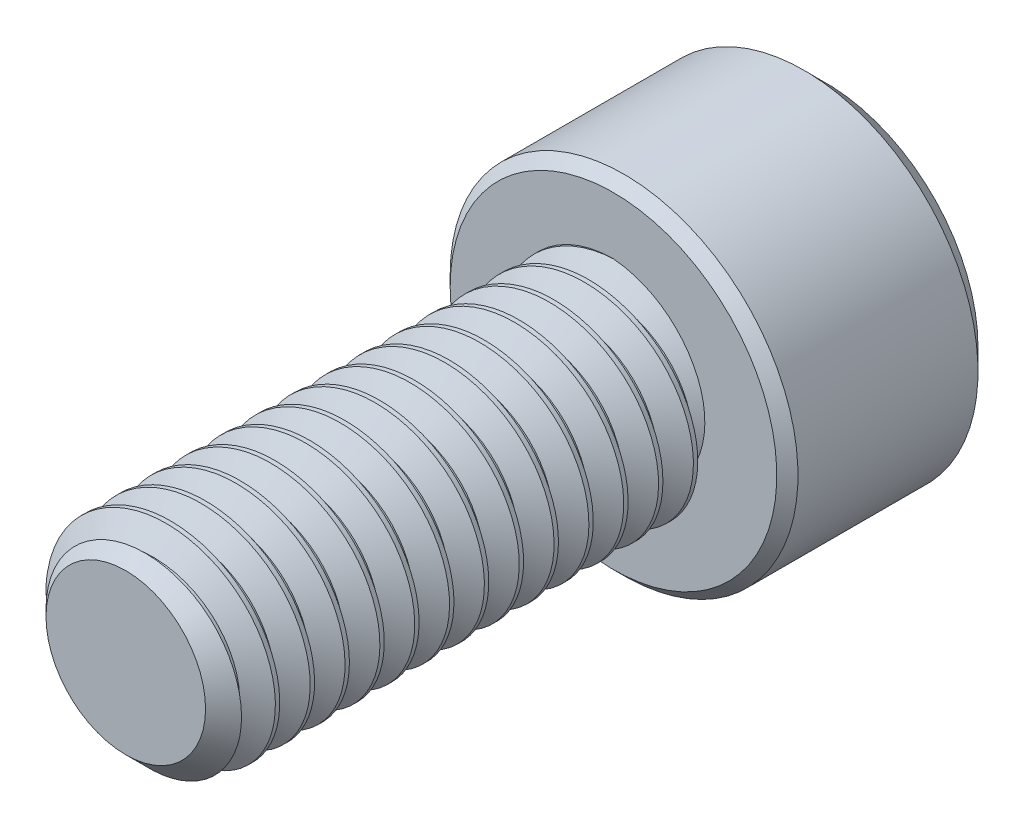
SolidWorks part; units mm, degrees
ref_plane "Front Plane" through (0, 0, 0) normal (0, 0, 1) x (1, 0, 0)
ref_plane "Top Plane" through (0, 0, 0) normal (0, 1, 0) x (1, 0, 0)
ref_plane "Right Plane" through (0, 0, 0) normal (1, 0, 0) x (0, 0, -1)
sketch "Sketch1" plane through (0, 0, 0) normal (0, 0, 1) x (1, 0, 0)
  line L0 (0, 2.413) -> (0, -2.413) construction
  circle A0 centre (0, 0) radius 2.413
  dimension "OD" = 4.826
extrude "Extrude1" add sketch "Sketch1" against normal blind 11.1125
sketch "Sketch2" plane through (0, 0, 0) normal (0, 0, 1) x (1, 0, 0)
  circle A0 centre (0, 0) radius 2.413 construction
  circle A1 centre (0, 0) radius 2.413
curve "Helix/Spiral1" pitch 0.7937 height 11.9062 turns 15 parameters "pitch"=0.7937
chamfer "Chamfer3" distance 0.5953 angle 45 1 edges at (2.413, 0, 0)
sketch "Sketch3" plane through (0, 0, 0) normal (1, 0, 0) x (0, 0, -1)
  line L0 (-0.6945, 2.413) -> (-0.3969, 1.8974)
  line L1 (-0.3969, 1.8974) -> (-0.2977, 1.8974)
  line L2 (-0.2977, 1.8974) -> (0, 2.413)
  line L3 (-0.6945, 2.413) -> (0, 2.413)
  line L4 (-0.3473, 2.413) -> (-0.3473, 1.8974) construction
  line L5 (-0.5457, 2.1552) -> (-0.1488, 2.1552) construction
  line L6 (0, 2.413) -> (0, -2.413) construction
  dimension "D1" = 0.0992
  dimension "D2" = 0.3969
  dimension "D3" = 60
sweep "Cut-Sweep1" cut profiles "Sketch3" path "Helix/Spiral1"
sketch "Sketch6" plane through (0, 0, -11.1125) normal (0, 0, -1) x (-1, 0, 0)
  circle A0 centre (0, 0) radius 3.9624
  dimension "head dia" = 7.9248
extrude "Extrude2" add sketch "Sketch6" along normal blind 4.826
sketch "Sketch7" plane through (0, 0, -15.9385) normal (0, 0, -1) x (-1, 0, 0)
  line L1 (0, 2.2914) -> (-1.9844, 1.1457)
  line L2 (-1.9844, 1.1457) -> (-1.9844, -1.1457)
  line L3 (-1.9844, -1.1457) -> (0, -2.2914)
  line L4 (0, -2.2914) -> (1.9844, -1.1457)
  line L5 (1.9844, -1.1457) -> (1.9844, 1.1457)
  line L6 (1.9844, 1.1457) -> (0, 2.2914)
  circle A0 centre (0, 0) radius 1.9844 construction
  dimension "hex dia" = 3.9688
extrude "Cut-Extrude1" cut sketch "Sketch7" against normal blind 2.9766
sketch "Sketch8" plane through (0, 0, -15.9385) normal (0, 0, -1) x (-1, 0, 0)
  circle A0 centre (0, 0) radius 2.2914
extrude "Cut-Extrude2" cut sketch "Sketch8" against normal blind 0.4826 draft 45
chamfer "Chamfer1" distance 0.4826 angle 45 1 edges at (-3.9624, 0, -15.9385)
chamfer "Chamfer2" distance 0.2413 angle 45 1 edges at (-3.9624, 0, -11.1125)
sketch "Sketch9" plane through (0, 0, 0) normal (1, 0, 0) x (0, 0, -1)
  line L0 (0, 2.413) -> (0, -2.413) construction
  line L1 (4.3656, 2.413) -> (4.3656, -2.413) construction
  line L2 (11.1125, 3.9624) -> (11.1125, -3.9624) construction
  line L3 (15.9385, 3.9624) -> (15.9385, -3.9624) construction
  line L4 (15.9385, 0) -> (0, 0) construction
  dimension "D1" = 4.3656
  dimension "D2" = 4.826
  dimension "D3" = 7.9248
  dimension "D4" = 11.1125
equation "\"D3@Helix/Spiral1\" = \"screw length@Extrude1\"+\"pitch@Helix/Spiral1\""
equation "\"D1@Sketch3\" = \"pitch@Helix/Spiral1\"*.125"
equation "\"D2@Sketch3\" = \"pitch@Helix/Spiral1\"*.5"
equation "\"D1@Cut-Extrude1\" = \"hex dia@Sketch7\"*.75"
equation "\"D1@Chamfer1\" = \"head depth@Extrude2\"/10"
equation "\"D1@Sketch9\" = \"pitch@Helix/Spiral1\"*5.5"
equation "\"D1@Chamfer2\" = \"D1@Chamfer1\"/2"
equation "\"D1@Cut-Extrude2\" = \"D1@Chamfer2\"*2"
equation "\"D1@Chamfer3\" = \"pitch@Helix/Spiral1\"*.750"
equation "\"D2@Sketch9\" = \"head depth@Extrude2\""
equation "\"D3@Sketch9\" = \"head dia@Sketch6\""
equation "\"D4@Sketch9\" = \"screw length@Extrude1\""
